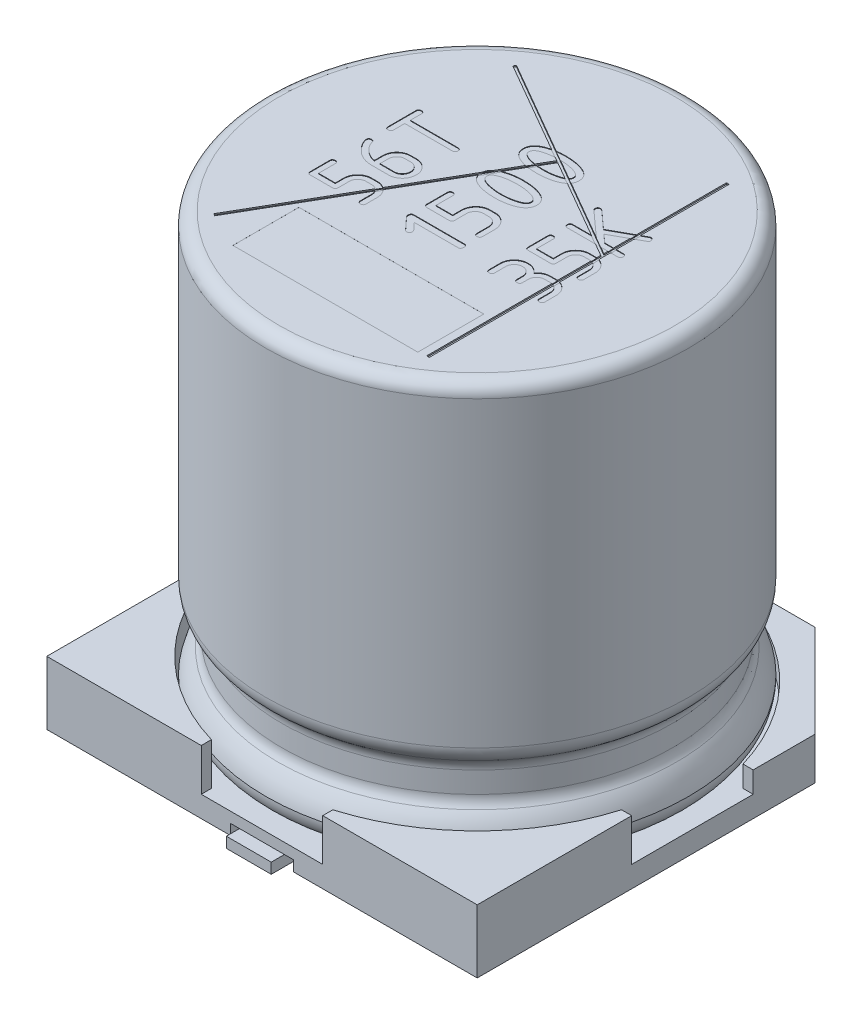
SolidWorks part; units mm, degrees
ref_plane "Front Plane" through (0, 0, 0) normal (0, 0, 1) x (1, 0, 0)
ref_plane "Top Plane" through (0, 0, 0) normal (0, 1, 0) x (1, 0, 0)
ref_plane "Right Plane" through (0, 0, 0) normal (1, 0, 0) x (0, 0, -1)
sketch "Sketch1" plane through (0, 0, 0) normal (0, 1, 0) x (1, 0, 0)
  line L0 (-8.15, 4.65) -> (-4.65, 8.15)
  line L1 (-4.65, 8.15) -> (4.65, 8.15)
  line L2 (-8.15, 4.65) -> (-8.15, -8.15)
  line L3 (-8.15, -8.15) -> (8.15, -8.15)
  line L4 (8.15, 4.65) -> (8.15, -8.15)
  line L5 (-8.15, 8.15) -> (8.15, -8.15) construction
  line L6 (-8.15, -8.15) -> (8.15, 8.15) construction
  line L7 (4.65, 8.15) -> (8.15, 4.65)
  point P0 (0, 0)
  dimension "D1" = 16.3
  dimension "D2" = 16.3
  dimension "D3" = 3.5
  dimension "D4" = 45
  dimension "D5" = 3.5
  dimension "D6" = 45
extrude "Boss-Extrude1" add sketch "Sketch1" along normal blind 2.4
sketch "Sketch2" plane through (0, 2.4, 0) normal (0, 1, 0) x (1, 0, 0)
  circle A0 centre (0, 0) radius 8.1
  dimension "D1" = 16.2
extrude "Cut-Extrude5" cut sketch "Sketch2" against normal blind 1.6
sketch "Sketch4" plane through (0, 0.8, 0) normal (0, 1, 0) x (1, 0, 0)
  line L1 (-2.3, 8.8833) -> (2.3, 8.8833)
  line L2 (-2.3, 8.8833) -> (-2.3, -8.8833)
  line L3 (-2.3, -8.8833) -> (2.3, -8.8833)
  line L4 (2.3, 8.8833) -> (2.3, -8.8833)
  line L5 (-2.3, 8.8833) -> (2.3, -8.8833) construction
  line L6 (-2.3, -8.8833) -> (2.3, 8.8833) construction
  line L7 (-9.4971, 2.3) -> (9.4971, 2.3)
  line L8 (-9.4971, 2.3) -> (-9.4971, -2.3)
  line L9 (-9.4971, -2.3) -> (9.4971, -2.3)
  line L10 (9.4971, 2.3) -> (9.4971, -2.3)
  line L11 (-9.4971, 2.3) -> (9.4971, -2.3) construction
  line L12 (-9.4971, -2.3) -> (9.4971, 2.3) construction
  point P0 (0, 0)
  point P6 (0, 0)
  circle M1 centre (0, 0) radius 8.1
  dimension "D1" = 4.6
  dimension "D2" = 4.6
extrude "Cut-Extrude6" cut sketch "Sketch4" along normal through all contours L2 L7 L4 M1 | L9 L2 L7 M1 | L8 L9 L7 M1 | L4 L1 L2 M1 | L10 L7 L9 M1 | L4 L9 L7 M1 | L9 L2 L4 M1 | L4 L2 L3 M1 | L2 L9 L4 L7 region at (0, 0.8, -8.4311) region at (0, 0.8, -5.1458) region at (0, 0.8, 0) region at (-5.1458, 0.8, 0) region at (-8.7402, 0.8, 0) region at (5.1458, 0.8, 0) region at (8.7402, 0.8, 0) region at (0, 0.8, 5.1458) region at (0, 0.8, 8.4311)
sketch "Sketch6" plane through (0, 2.4, 0) normal (0, 1, 0) x (1, 0, 0)
  line L1 (-8.8264, 8.7608) -> (8.8264, 8.7608)
  line L2 (-8.8264, 8.7608) -> (-8.8264, 0.5886)
  line L3 (-8.8264, 0.5886) -> (8.8264, 0.5886)
  line L4 (8.8264, 8.7608) -> (8.8264, 0.5886)
  line L5 (-8.8264, 8.7608) -> (8.8264, 0.5886) construction
  line L6 (-8.8264, 0.5886) -> (8.8264, 8.7608) construction
  point P0 (0, 4.6747)
extrude "Cut-Extrude8" cut sketch "Sketch6" against normal blind 0.8
sketch "Sketch7" plane through (0, 0, 0) normal (0, -1, 0) x (1, 0, 0)
  line L0 (-8.15, 0) -> (8.15, 0) construction
  line L1 (-1.2, 3.5) -> (1.2, 3.5)
  line L2 (-1.2, 3.5) -> (-1.2, 9.9192)
  line L3 (-1.2, 9.9192) -> (1.2, 9.9192)
  line L4 (1.2, 3.5) -> (1.2, 9.9192)
  line L5 (-8.15, -4.65) -> (-8.15, 8.15) construction
  line L6 (8.15, 8.15) -> (8.15, -4.65) construction
  line L7 (1.2, -3.5) -> (1.2, -9.9192)
  line L8 (-1.2, -9.9192) -> (1.2, -9.9192)
  line L9 (-1.2, -3.5) -> (-1.2, -9.9192)
  line L10 (-1.2, -3.5) -> (1.2, -3.5)
  circle A0 centre (0, 3.5) radius 1.2
  circle A1 centre (0, -3.5) radius 1.2
  line M2 (8.15, 8.15) -> (-8.15, 8.15)
  line M5 (-4.65, -8.15) -> (4.65, -8.15)
  dimension "D1" = 2.4
  dimension "D2" = 3.5
extrude "Cut-Extrude9" cut sketch "Sketch7" against normal blind 0.4 contours A0 L4 L2 M2 | L4 L3 L2 M2 | L1 A0 | L1 A0 | A1 L10 | A1 L10 | L7 A1 L9 M5 | L9 L8 L7 M5 region at (0, 0, 4.0093) region at (0, 0, 6.2866) region at (0, 0, 2.9907) region at (0, 0, 9.0346) region at (0, 0, -4.0093) region at (0, 0, -2.9907) region at (0, 0, -6.2866) region at (0, 0, -9.0346)
sketch "Sketch8" plane through (0, 0.4, 0) normal (0, -1, 0) x (1, 0, 0)
  line L1 (0.85, 3.5) -> (-0.85, 3.5)
  line L2 (0.85, 3.5) -> (0.85, 8.65)
  line L3 (0.85, 8.65) -> (-0.85, 8.65)
  line L4 (-0.85, 3.5) -> (-0.85, 8.65)
  line L5 (0.85, -3.5) -> (-0.85, -3.5)
  line L6 (0.85, -3.5) -> (0.85, -8.65)
  line L7 (0.85, -8.65) -> (-0.85, -8.65)
  line L8 (-0.85, -3.5) -> (-0.85, -8.65)
  circle A0 centre (0, 3.5) radius 0.85
  circle A1 centre (0, -3.5) radius 0.85
  line M1 (1.2, 8.15) -> (-1.2, 8.15)
  dimension "D1" = 1.7
  dimension "D2" = 1.7
  dimension "D3" = 1.7
  dimension "D4" = 1.7
  dimension "D5" = 17.3
extrude "Boss-Extrude2" add sketch "Sketch8" along direction (0, 1, 0) on the side of the normal blind 0.4 contours L4 L2 L3 M1 | A0 L2 L4 M1 | L1 A0 | L1 A0 | L5 A1 | L5 A1 | A1 L8 L7 L6 region at (0, 0.4, 3.1392) region at (0, 0.4, 6.1543) region at (0, 0.4, 3.8608) region at (0, 0.4, 8.4) region at (0, 0.4, -3.8608) region at (0, 0.4, -3.1392) region at (0, 0.4, -6.4048)
sketch "Sketch9" plane through (0, 0, 0) normal (0, -1, 0) x (1, 0, 0)
  line L1 (5, -5) -> (-5, -5) construction
  line L2 (5, -5) -> (5, 5) construction
  line L3 (5, 5) -> (-5, 5) construction
  line L4 (-5, -5) -> (-5, 5) construction
  line L5 (5, -5) -> (-5, 5) construction
  line L6 (5, 5) -> (-5, -5) construction
  circle A0 centre (-5, 5) radius 0.75
  circle A1 centre (-5, -5) radius 0.75
  circle A2 centre (5, 5) radius 0.75
  circle A3 centre (5, -5) radius 0.75
  circle A4 centre (0, 0) radius 0.75
  point P0 (0, 0)
  dimension "D3" = 1.5
  dimension "D4" = 1.5
  dimension "D5" = 1.5
  dimension "D1" = 10
  dimension "D2" = 10
extrude "Boss-Extrude3" add sketch "Sketch9" along normal blind 0.2
sketch "Sketch10" plane through (0, 0, 0) normal (0, -1, 0) x (1, 0, 0)
  line L0 (0, 2.3) -> (0, -2.3) construction
  circle A0 centre (3.4, 0) radius 1.75
  arc A1 (-1.2, 3.5) -> (1.2, 3.5) centre (0, 3.5) ccw construction
  arc A2 (1.2, -3.5) -> (-1.2, -3.5) centre (0, -3.5) ccw construction
  circle A3 centre (-3.4, 0) radius 1.75
  dimension "D1" = 3.5
  dimension "D2" = 3.4
extrude "Cut-Extrude10" cut sketch "Sketch10" against normal blind 0.05
sketch "Sketch11" plane through (0, 0.05, 0) normal (0, -1, 0) x (1, 0, 0)
  text T0 "S  " font "Century Gothic" height in points 8
extrude "Boss-Extrude4" add sketch "Sketch11" along normal blind 0.05
sketch "Sketch12" plane through (0, 0.05, 0) normal (0, -1, 0) x (1, 0, 0)
  text T0 "12" font "ISOCP2" height in points 6
extrude "Boss-Extrude5" add sketch "Sketch12" along normal blind 0.05
ref_plane "Plane1" through (0, 1, 0) normal (0, 1, 0) x (1, 0, 0)
sketch "Sketch13" plane through (0, 1, 0) normal (0, 1, 0) x (1, 0, 0)
  circle A0 centre (0, 0) radius 8
  dimension "D1" = 16
extrude "Boss-Extrude6" add sketch "Sketch13" along normal blind 16 separate body
sketch "Sketch14" plane through (0, 0, 0) normal (0, 0, 1) x (1, 0, 0)
  line L0 (0, 0) -> (0, 17) construction
  line L1 (8, 17) -> (-8, 17) construction
  line L5 (8, 3.1) -> (8, 3.9) construction
  line L6 (8, 1) -> (8, 17) construction
  line L7 (7.4, 3.1) -> (7.4, 3.9)
  line L8 (8.6, 3.1) -> (8.6, 3.9)
  line L9 (1.2, 0) -> (8.15, 0) construction
  arc A0 (7.4, 3.1) -> (8.6, 3.1) centre (8, 3.1) ccw
  arc A1 (8.6, 3.9) -> (7.4, 3.9) centre (8, 3.9) ccw
  point P9 (8, 3.5)
  dimension "D1" = 3.5
  dimension "D3" = 1.2
  dimension "D2" = 0.8
revolve "Cut-Revolve3" cut sketch "Sketch14" angle 360 about L0
fillet "Fillet3" radius 0.8 2 edges at (0, 4.5, -8) (0, 1, 8)
fillet "Fillet5" radius 2 1 edges at (0, 2.5, 8)
fillet "Fillet6" radius 0.5 1 edges at (0, 17, 8)
sketch "Sketch15" plane through (0, 17, 0) normal (0, 1, 0) x (1, 0, 0)
  line L1 (-3.5, -3.25) -> (3.5, -3.25)
  line L2 (-3.5, -3.25) -> (-3.5, -5.75)
  line L3 (-3.5, -5.75) -> (3.5, -5.75)
  line L4 (3.5, -3.25) -> (3.5, -5.75)
  line L5 (-3.5, -3.25) -> (3.5, -5.75) construction
  line L6 (-3.5, -5.75) -> (3.5, -3.25) construction
  point P0 (0, -4.5)
  dimension "D1" = 4.5
  dimension "D2" = 7
  dimension "D3" = 2.5
extrude "Cut-Extrude11" cut sketch "Sketch15" against normal blind 0.001
sketch "Sketch16" plane through (0, 17, 0) normal (0, 1, 0) x (1, 0, 0)
  line L0 (3.7898, 1.0041) -> (-4.0374, 5.5232)
  line L1 (3.7898, -5.7049) -> (3.8898, -5.7049)
  line L2 (3.7898, -5.7049) -> (3.7898, 5.6491)
  line L3 (3.7898, 5.6491) -> (3.8898, 5.6491)
  line L4 (3.8898, -5.7049) -> (3.8898, 5.6491)
  line L5 (3.7898, 0.8887) -> (-4.0874, 5.4366)
  line L6 (-4.0874, 5.4366) -> (-4.0374, 5.5232)
  line L7 (-0.0622, 3.1126) -> (-4.8166, -5.1224)
  line L8 (-0.1488, 3.1626) -> (-4.9004, -5.0674)
  line L9 (-4.9004, -5.0674) -> (-4.8166, -5.1224)
  dimension "D1" = 0.1
  dimension "D2" = 60
  dimension "D3" = 0.1
  dimension "D4" = 0.1
extrude "Cut-Extrude12" cut sketch "Sketch16" against normal blind 0.05 contours L1 L4 L3 L2 | L6 L5 L2 L0 | L8 L9 L7 L5 region at (-0.1363, 17, -3.2131) region at (3.8398, 17, 0.0279) region at (-2.482, 17, 0.9786)
sketch "Sketch21" plane through (0, 17, 0) normal (0, 1, 0) x (1, 0, 0)
  line L0 (-2.3401, 2.4694) -> (-2.3401, -2.8222) construction
  line L1 (0.9356, 3.7293) -> (0.9356, -2.8222) construction
  line L2 (4.2618, -2.0158) -> (4.2618, 4.4852) construction
  text T0 "56T" font "ISOCPEUR" height in points 6
  text T1 " 1500" font "ISOCPEUR" height in points 6
  text T2 "35K" font "ISOCPEUR" height in points 6
extrude "Cut-Extrude13" cut sketch "Sketch21" against normal blind 0.02
